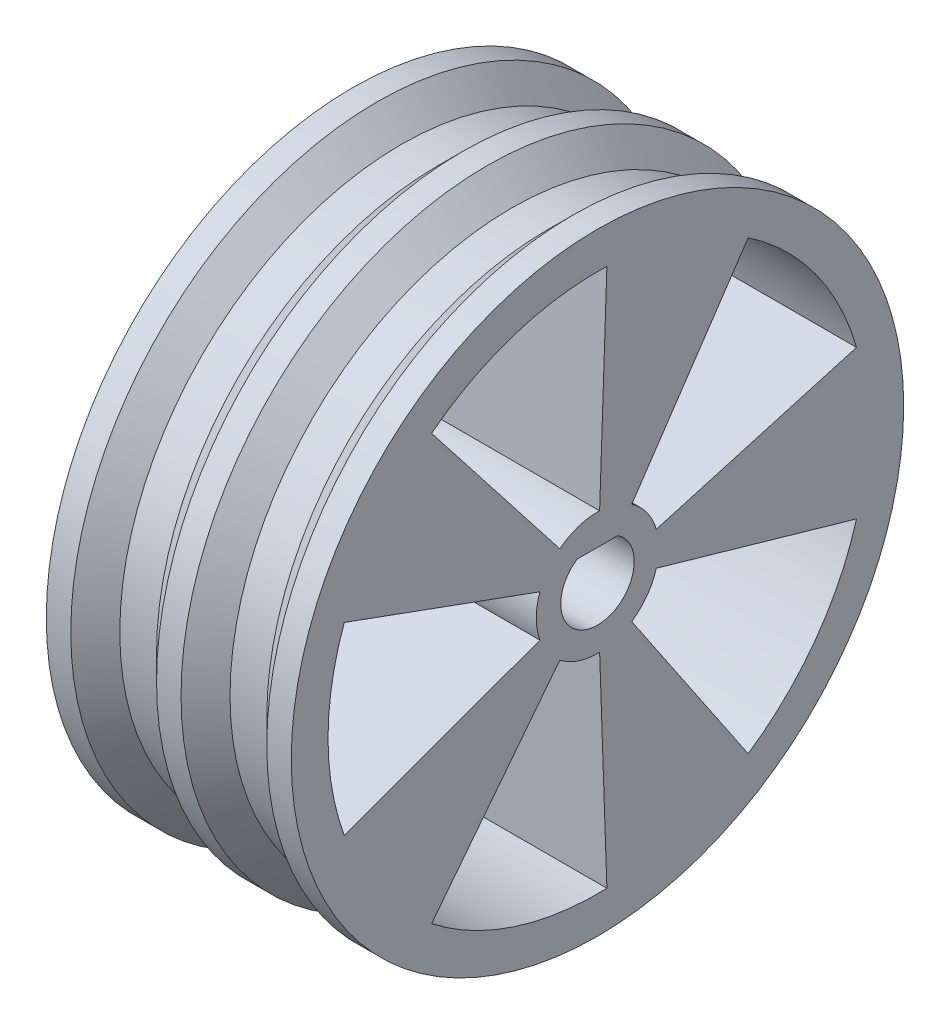
SolidWorks part; units mm, degrees
ref_plane "Plan de face" through (0, 0, 0) normal (0, 0, 1) x (1, 0, 0)
ref_plane "Plan de dessus" through (0, 0, 0) normal (0, 1, 0) x (1, 0, 0)
ref_plane "Plan de droite" through (0, 0, 0) normal (1, 0, 0) x (0, 0, -1)
sketch "Esquisse1" plane through (0, 0, 0) normal (1, 0, 0) x (0, 0, -1)
  line L0 (-1.6583, 2.5) -> (1.6583, 2.5)
  line L1 (0, 0) -> (0, 4.7784) construction
  arc A0 (-1.6583, 2.5) -> (1.6583, 2.5) centre (0, 0) ccw
  circle A1 centre (0, 0) radius 25
  point P6 (0, 3)
  dimension "D1" = 6
  dimension "D3" = 50
  dimension "D2" = 0.5
extrude "BASE" add sketch "Esquisse1" along normal blind 10 and the other way blind 10
ref_plane "PLAN GORGE" through (-8, 0, 0) normal (-1, 0, 0) x (0, 0, 1)
sketch "Esquisse2" plane through (-8, 0, 0) normal (-1, 0, 0) x (0, 0, 1)
  circle A0 centre (0, 0) radius 25
  circle A1 centre (0, 0) radius 23
  circle A5 centre (0, 0) radius 25 construction
  dimension "D1" = 2
extrude "VIDE GORGE" cut sketch "Esquisse2" against normal blind 7
mirror "SYM GORGE" about plane through (0, 0, 0) normal (1, 0, 0) of "VIDE GORGE"
sketch "Esquisse4" plane through (10, 0, 0) normal (1, 0, 0) x (0, 0, -1)
  line L0 (0, 0) -> (-22, 0) construction
  line L1 (-4.6985, 1.7101) -> (-20.6732, 7.5244)
  line L2 (-4.6985, -1.7101) -> (-20.6732, -7.5244)
  line L3 (0.1745, 4.997) -> (0.7678, 21.9866)
  line L4 (-3.0783, 3.9401) -> (-13.5446, 17.3362)
  line L5 (4.8063, 1.3782) -> (21.1478, 6.064)
  line L6 (2.796, 4.1452) -> (12.3022, 18.2388)
  line L7 (2.796, -4.1452) -> (12.3022, -18.2388)
  line L8 (4.8063, -1.3782) -> (21.1478, -6.064)
  line L9 (-3.0783, -3.9401) -> (-13.5446, -17.3362)
  line L10 (0.1745, -4.997) -> (0.7678, -21.9866)
  circle A0 centre (0, 0) radius 5
  arc A1 (-20.6732, 7.5244) -> (-20.6732, -7.5244) centre (0, 0) ccw
  circle A2 centre (0, 0) radius 25 construction
  arc A3 (0.7678, 21.9866) -> (-13.5446, 17.3362) centre (0, 0) ccw
  arc A4 (21.1478, 6.064) -> (12.3022, 18.2388) centre (0, 0) ccw
  arc A5 (12.3022, -18.2388) -> (21.1478, -6.064) centre (0, 0) ccw
  arc A6 (-13.5446, -17.3362) -> (0.7678, -21.9866) centre (0, 0) ccw
  point P30 (0, 0)
  dimension "D1" = 3
  dimension "D2" = 10
  dimension "D3" = 20
  dimension "D4" = 20
  dimension "D5" = 5
extrude "VIDE JANTE" cut sketch "Esquisse4" against normal up to surface (20 mm away) contours L0 A0 L1 A1 | A0 L0 A1 L2 | L3 A3 L4 A0 | L5 A4 L6 A0 | L7 A5 L8 A0 | L9 A6 L10 A0 region at (10, -2.6406, 14.9755) region at (10, 2.6406, 14.9755) region at (10, 14.2425, 4.6277) region at (10, -14.2425, 4.6277) region at (10, 8.8023, -12.1154) region at (10, -8.8023, -12.1154) up to face at (-10, -0.25, 0)
sketch "Esquisse6" plane through (-10, 0, 0) normal (-1, 0, 0) x (0, 0, 1)
  circle A0 centre (0, 0) radius 3
extrude "VIDE BLOC AXE" cut sketch "Esquisse6" against normal blind 4
chamfer "CHAN" distance 2 angle 45 4 edges at (-8, 0, 23) (-1, 0, 23) (1, 0, 23) (8, 0, 23)
